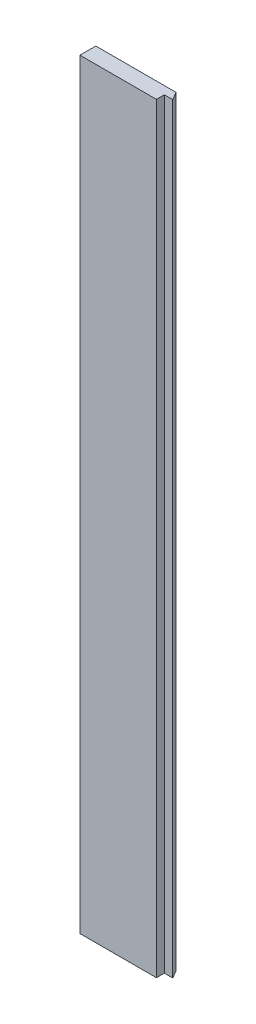
SolidWorks part; units mm, degrees
ref_plane "Front Plane" through (0, 0, 0) normal (0, 0, 1) x (1, 0, 0)
ref_plane "Top Plane" through (0, 0, 0) normal (0, 1, 0) x (1, 0, 0)
ref_plane "Right Plane" through (0, 0, 0) normal (1, 0, 0) x (0, 0, -1)
sketch "Sketch1" plane through (0, 0, 0) normal (0, 1, 0) x (1, 0, 0)
  line L0 (-60, 0) -> (-41.5, 0)
  line L1 (-60, 9) -> (60, 9)
  line L2 (-60, 9) -> (-60, -9)
  line L3 (-60, -9) -> (60, -9)
  line L4 (60, 9) -> (60, -9)
  line L5 (-60, 9) -> (60, -9) construction
  line L6 (-60, -9) -> (60, 9) construction
  line L7 (-41.5, 0) -> (-36.3038, 9)
  line L8 (-41.5, 0) -> (-41.5, 9) construction
  line L9 (60, 0) -> (54.8038, 9)
  line L10 (60, 0) -> (50.5, 0)
  line L11 (50.5, 0) -> (50.5, -9)
  line L13 (0, 9) -> (0, -9) construction
  point P0 (0, 0)
  dimension "D1" = 120
  dimension "D2" = 18
  dimension "D3" = 18.5
  dimension "D4" = 30
  dimension "D5" = 9.5
  dimension "D6" = 30
extrude "Shape" add sketch "Sketch1" along normal blind 1000 contours L3 L11 L10 L9 L1 L7 L0 L2 region at (1.7695, 0, 0.3466)
ref_plane "Plane1" [suppressed] through (-60, 790, 9) normal (0.5851, -0.811, 0) x (-0.811, -0.5851, 0)
sketch "Sketch3" [suppressed] plane through (0, 0, 9) normal (0, 0, 1) x (1, 0, 0)
  line L1 (-60, 790) -> (445, 90) construction
  line L3 (-60, 790) -> (445, 90)
  line L6 (50.5, 0) -> (60, 0)
  line L7 (60, 0) -> (60, 800)
  line L8 (60, 800) -> (50.5, 800)
  line L9 (50.5, 800) -> (50.5, 0)
  line L10 (50.5, 0) -> (60, 0)
  line L11 (60, 0) -> (60, 800)
  line L12 (60, 800) -> (50.5, 800)
  line L13 (50.5, 800) -> (50.5, 0)
  dimension "D1" = 0
extrude "Cut-Extrude1" [suppressed] cut sketch "Sketch3" against normal up to next
sketch "Sketch4" [suppressed] plane through (0, 0, 9) normal (0, 0, 1) x (1, 0, 0)
  line L0 (-170.5, 790) -> (334.5, 90) construction
  line L1 (-170.5, 790) -> (334.5, 90)
  line L6 (50.5, 0) -> (60, 0)
  line L7 (60, 0) -> (60, 800)
  line L8 (60, 800) -> (50.5, 800)
  line L9 (50.5, 800) -> (50.5, 0)
  line L10 (50.5, 0) -> (60, 0)
  line L11 (60, 0) -> (60, 800)
  line L12 (60, 800) -> (50.5, 800)
  line L13 (50.5, 800) -> (50.5, 0)
  dimension "D1" = 0
extrude "Cut-Extrude2" [suppressed] cut sketch "Sketch4" against normal through all and the other way through all
sketch "Sketch5" [suppressed] plane through (0, 0, 9) normal (0, 0, 1) x (1, 0, 0)
  line L0 (-281, 790) -> (224, 90) construction
  line L1 (-281, 790) -> (224, 90)
  line L4 (50.5, 0) -> (60, 0)
  line L5 (60, 0) -> (60, 800)
  line L6 (60, 800) -> (50.5, 800)
  line L7 (50.5, 800) -> (50.5, 0)
  line L8 (50.5, 0) -> (60, 0)
  line L9 (60, 0) -> (60, 800)
  line L10 (60, 800) -> (50.5, 800)
  line L11 (50.5, 800) -> (50.5, 0)
  dimension "D1" = 0
extrude "Cut-Extrude3" [suppressed] cut sketch "Sketch5" against normal up to next
sketch "Sketch6" [suppressed] plane through (0, 0, 9) normal (0, 0, 1) x (1, 0, 0)
  line L0 (-391.5, 790) -> (113.5, 90) construction
  line L1 (-391.5, 790) -> (113.5, 90)
  line L6 (50.5, 0) -> (60, 0)
  line L7 (60, 0) -> (60, 800)
  line L8 (60, 800) -> (50.5, 800)
  line L9 (50.5, 800) -> (50.5, 0)
  line L10 (50.5, 0) -> (60, 0)
  line L11 (60, 0) -> (60, 800)
  line L12 (60, 800) -> (50.5, 800)
  line L13 (50.5, 800) -> (50.5, 0)
  dimension "D1" = 0
extrude "Cut-Extrude4" [suppressed] cut sketch "Sketch6" against normal up to next
sketch "Sketch7" [suppressed] plane through (0, 0, 9) normal (0, 0, 1) x (1, 0, 0)
  line L0 (-502, 790) -> (3, 90) construction
  line L1 (-502, 790) -> (3, 90)
  line L2 (3, 90) -> (3, 0)
  line L3 (-60, 0) -> (50.5, 0) construction
  line L8 (50.5, 0) -> (60, 0)
  line L9 (60, 0) -> (60, 800)
  line L10 (60, 800) -> (50.5, 800)
  line L11 (50.5, 800) -> (50.5, 0)
  line L12 (50.5, 0) -> (60, 0)
  line L13 (60, 0) -> (60, 800)
  line L14 (60, 800) -> (50.5, 800)
  line L15 (50.5, 800) -> (50.5, 0)
  line M5 (-60, 0) -> (50.5, 0)
  line M6 (50.5, 0) -> (50.5, 800)
  line M7 (50.5, 800) -> (-60, 800)
  line M8 (-60, 800) -> (-60, 0)
  dimension "D1" = 0
extrude "Cut-Extrude5" [suppressed] cut sketch "Sketch7" against normal up to next contours L1 L2 M5 M6 M7 M8 | L13 L14 L12 M6
sketch "Sketch8" [suppressed] plane through (0, 0, -9) normal (0, 0, -1) x (-1, 0, 0)
  line L1 (-730.5, 863.1483) -> (129.5, 863.1483) construction
  line L8 (-730.5, 863.1483) -> (129.5, 863.1483)
  line L9 (-50.5, 0) -> (-60, 0) construction
  line L10 (-60, 0) -> (-60, 1000) construction
  line L11 (-60, 1000) -> (-50.5, 1000) construction
  line L12 (-50.5, 1000) -> (-50.5, 0) construction
  line L13 (-54.8038, 0) -> (36.3038, 0) construction
  line L14 (36.3038, 1000) -> (-54.8038, 1000) construction
  line L15 (-54.8038, 1000) -> (-54.8038, 0) construction
  line L16 (36.3038, 0) -> (41.5, 0) construction
  line L17 (41.5, 1000) -> (36.3038, 1000) construction
  line L18 (41.5, 0) -> (60, 0) construction
  line L19 (60, 0) -> (60, 1000) construction
  line L20 (60, 1000) -> (41.5, 1000) construction
  line L21 (-50.5, 0) -> (-60, 0)
  line L22 (-60, 0) -> (-60, 1000)
  line L23 (-60, 1000) -> (-50.5, 1000)
  line L24 (-50.5, 1000) -> (-50.5, 0)
  line L25 (-54.8038, 0) -> (36.3038, 0)
  line L26 (36.3038, 1000) -> (-54.8038, 1000)
  line L27 (-54.8038, 1000) -> (-54.8038, 0)
  line L28 (36.3038, 0) -> (41.5, 0)
  line L29 (41.5, 1000) -> (36.3038, 1000)
  line L30 (41.5, 0) -> (60, 0)
  line L31 (60, 0) -> (60, 1000)
  line L32 (60, 1000) -> (41.5, 1000)
extrude "Cut-Extrude6" [suppressed] cut sketch "Sketch8" against normal up to next
sketch "Sketch9" [suppressed] plane through (0, 0, -9) normal (0, 0, -1) x (-1, 0, 0)
  line L0 (-60, 1000) -> (-60, 0) construction
  line L1 (60, 1000) -> (-60, 1000)
  line L2 (60, 1000) -> (60, 863.1483)
  line L3 (60, 863.1483) -> (-60, 863.1483)
  line L4 (-60, 1000) -> (-60, 863.1483)
  line L5 (-841, 863.1483) -> (19, 863.1483) construction
  point P9 (0, 863.1483)
extrude "Cut-Extrude7" [suppressed] cut sketch "Sketch9" against normal up to next
sketch "Sketch10" plane through (0, 0, -9) normal (0, 0, -1) x (-1, 0, 0)
  line L0 (36.3038, 0) -> (-54.8038, 0) construction
  line L1 (36.3038, 1000) -> (60, 1000)
  line L2 (36.3038, 1000) -> (36.3038, 0)
  line L3 (36.3038, 0) -> (60, 0)
  line L4 (60, 1000) -> (60, 0)
  line L5 (60, 1000) -> (60, 0) construction
  line L7 (-60, 1000) -> (-60, 0) construction
  line L8 (60, 1000) -> (-60, 1000)
  line L9 (60, 1000) -> (60, 863.1483)
  line L10 (60, 863.1483) -> (-60, 863.1483)
  line L11 (-60, 1000) -> (-60, 863.1483)
  line L12 (-643.6962, 863.1483) -> (216.3038, 863.1483) construction
  line M4 (36.3038, 0) -> (36.3038, 1000)
  line M5 (36.3038, 1000) -> (-54.8038, 1000)
  line M6 (-54.8038, 1000) -> (-54.8038, 0)
extrude "Cut-Extrude8" cut sketch "Sketch10" against normal up to next contours L8 L11 L10 M6 | L10 L2 M5 M6 | L10 L4 L1 L2 | L4 L10 L3 M4 region at (-48.1519, 931.5742, -9) region at (9.25, 931.5742, -9) region at (-48.1519, 431.5742, -9) region at (57.4019, 931.5742, -9)
